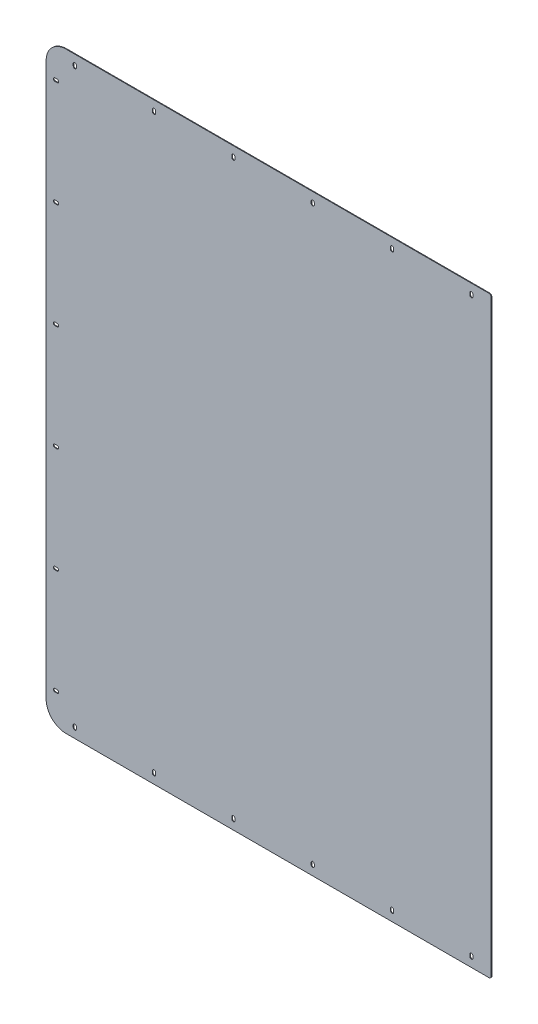
SolidWorks part; units mm, degrees
material "Q235-A"
ref_plane "前视基准面" through (0, 0, 0) normal (0, 0, 1) x (1, 0, 0)
ref_plane "上视基准面" through (0, 0, 0) normal (0, 1, 0) x (1, 0, 0)
ref_plane "右视基准面" through (0, 0, 0) normal (1, 0, 0) x (0, 0, -1)
sketch "草图1" plane through (0, 0, 0) normal (0, 0, 1) x (1, 0, 0)
  line L1 (505, -672.5) -> (-505, -672.5)
  line L2 (505, -672.5) -> (505, 672.5)
  line L3 (505, 672.5) -> (-505, 672.5)
  line L4 (-505, -672.5) -> (-505, 672.5)
  line L5 (505, -672.5) -> (-505, 672.5) construction
  line L6 (505, 672.5) -> (-505, -672.5) construction
  point P0 (0, 0)
  dimension "D1" = 1345
  dimension "D2" = 1010
base flange "基体-法兰1" sketch "草图1" thickness 1.5 reverse thickness direction no parameters "D1"=0.7366
fillet "圆角1" radius 45 2 edges at (-505, -672.5, -0.75) (-505, 672.5, -0.75)
fillet "圆角2" radius 5 2 edges at (505, -672.5, -0.75) (505, 672.5, -0.75)
sketch "草图2" plane through (0, 0, 0) normal (0, 0, 1) x (1, 0, 0)
  line L0 (-485, -600) -> (-480, -600) construction
  line L1 (-485, -596.5) -> (-480, -596.5)
  line L2 (-485, -603.5) -> (-480, -603.5)
  line L3 (-505, 627.5) -> (-505, -627.5) construction
  line L4 (-460, -672.5) -> (500, -672.5) construction
  arc A0 (-485, -596.5) -> (-485, -603.5) centre (-485, -600) ccw
  arc A1 (-480, -603.5) -> (-480, -596.5) centre (-480, -600) ccw
  point P2 (-482.5, -600)
  dimension "D1" = 7
  dimension "D2" = 5
  dimension "D3" = 22.5
  dimension "D4" = 72.5
extrude "切除-拉伸1" cut sketch "草图2" against normal blind 10 normal cut yes
pattern_linear "阵列(线性)1" count 6 spacing 240 along (0, 1, 0) of "切除-拉伸1"
sketch "草图3" plane through (0, 0, 0) normal (0, 0, 1) x (1, 0, 0)
  line L0 (-440, 652.5) -> (-440, 647.5) construction
  line L1 (-436.5, 652.5) -> (-436.5, 647.5)
  line L2 (-443.5, 652.5) -> (-443.5, 647.5)
  line L3 (-440, -647.5) -> (-440, -652.5) construction
  line L4 (-436.5, -647.5) -> (-436.5, -652.5)
  line L5 (-443.5, -647.5) -> (-443.5, -652.5)
  line L6 (-460, -672.5) -> (500, -672.5) construction
  line L7 (-505, 627.5) -> (-505, -627.5) construction
  line L8 (500, 672.5) -> (-460, 672.5) construction
  arc A0 (-436.5, 652.5) -> (-443.5, 652.5) centre (-440, 652.5) ccw
  arc A1 (-443.5, 647.5) -> (-436.5, 647.5) centre (-440, 647.5) ccw
  arc A2 (-436.5, -647.5) -> (-443.5, -647.5) centre (-440, -647.5) ccw
  arc A3 (-443.5, -652.5) -> (-436.5, -652.5) centre (-440, -652.5) ccw
  point P2 (-440, 650)
  point P8 (-440, -650)
  dimension "D1" = 7
  dimension "D2" = 5
  dimension "D3" = 22.5
  dimension "D4" = 7
  dimension "D5" = 5
  dimension "D6" = 65
  dimension "D7" = 22.5
extrude "切除-拉伸2" cut sketch "草图3" against normal blind 10 normal cut yes
pattern_linear "阵列(线性)2" count 6 spacing 180 along (1, 0, 0) of "切除-拉伸2"
sketch "折弯-线1" [suppressed] plane through (0, 0, 0) normal (0, 1, 0) x (1, 0, 0)
sketch "边界框1" [suppressed] plane through (0, 0, 0) normal (0, 1, 0) x (1, 0, 0)
sheet metal parameters "钣金1" thickness 1.5 parameters "D1"=0.7366
flat pattern "平板型式1" [suppressed]
sketch "折弯-线2" plane through (0, 0, 0) normal (0, 1, 0) x (1, 0, 0)
sketch3d "边界框2" [suppressed]
  line L0 (257.5, -672.5, 0) -> (257.5, 672.5, 0) construction
  line L1 (-257.5, -672.5, 0) -> (-257.5, 672.5, 0) construction
  line L2 (257.5, -672.5, 0) -> (-257.5, -672.5, 0) construction
  line L3 (257.5, 672.5, 0) -> (-257.5, 672.5, 0) construction
sheet metal parameters "钣金2" thickness 1.5 parameters "D1"=0.7366
flat pattern "平板型式1"
sketch "折弯-线2" plane through (0, 0, 0) normal (0, 1, 0) x (1, 0, 0)
sketch3d "边界框2" [suppressed]
  line L0 (257.5, -672.5, 0) -> (257.5, 672.5, 0) construction
  line L1 (-257.5, -672.5, 0) -> (-257.5, 672.5, 0) construction
  line L2 (257.5, -672.5, 0) -> (-257.5, -672.5, 0) construction
  line L3 (257.5, 672.5, 0) -> (-257.5, 672.5, 0) construction
sheet metal parameters "钣金3" thickness 1.5 parameters "D1"=0.7366
flat pattern "平板型式1"
sketch "折弯-线2" plane through (0, 0, 0) normal (0, 1, 0) x (1, 0, 0)
sketch3d "边界框2" [suppressed]
  line L0 (257.5, -672.5, 0) -> (257.5, 672.5, 0) construction
  line L1 (-257.5, -672.5, 0) -> (-257.5, 672.5, 0) construction
  line L2 (257.5, -672.5, 0) -> (-257.5, -672.5, 0) construction
  line L3 (257.5, 672.5, 0) -> (-257.5, 672.5, 0) construction
sheet metal parameters "钣金4" thickness 1.5 parameters "D1"=0.7366
flat pattern "平板型式1"
sketch "折弯-线2" plane through (0, 0, 0) normal (0, 1, 0) x (1, 0, 0)
sketch3d "边界框2" [suppressed]
  line L0 (257.5, -672.5, 0) -> (257.5, 672.5, 0) construction
  line L1 (-257.5, -672.5, 0) -> (-257.5, 672.5, 0) construction
  line L2 (257.5, -672.5, 0) -> (-257.5, -672.5, 0) construction
  line L3 (257.5, 672.5, 0) -> (-257.5, 672.5, 0) construction
sheet metal parameters "钣金5" thickness 1.5 parameters "D1"=0.7366
flat pattern "平板型式1"
sketch "折弯-线2" plane through (0, 0, 0) normal (0, 1, 0) x (1, 0, 0)
sketch3d "边界框2" [suppressed]
  line L0 (505, -672.5, 0) -> (505, 672.5, 0) construction
  line L1 (-505, -672.5, 0) -> (-505, 672.5, 0) construction
  line L2 (505, -672.5, 0) -> (-505, -672.5, 0) construction
  line L3 (505, 672.5, 0) -> (-505, 672.5, 0) construction
